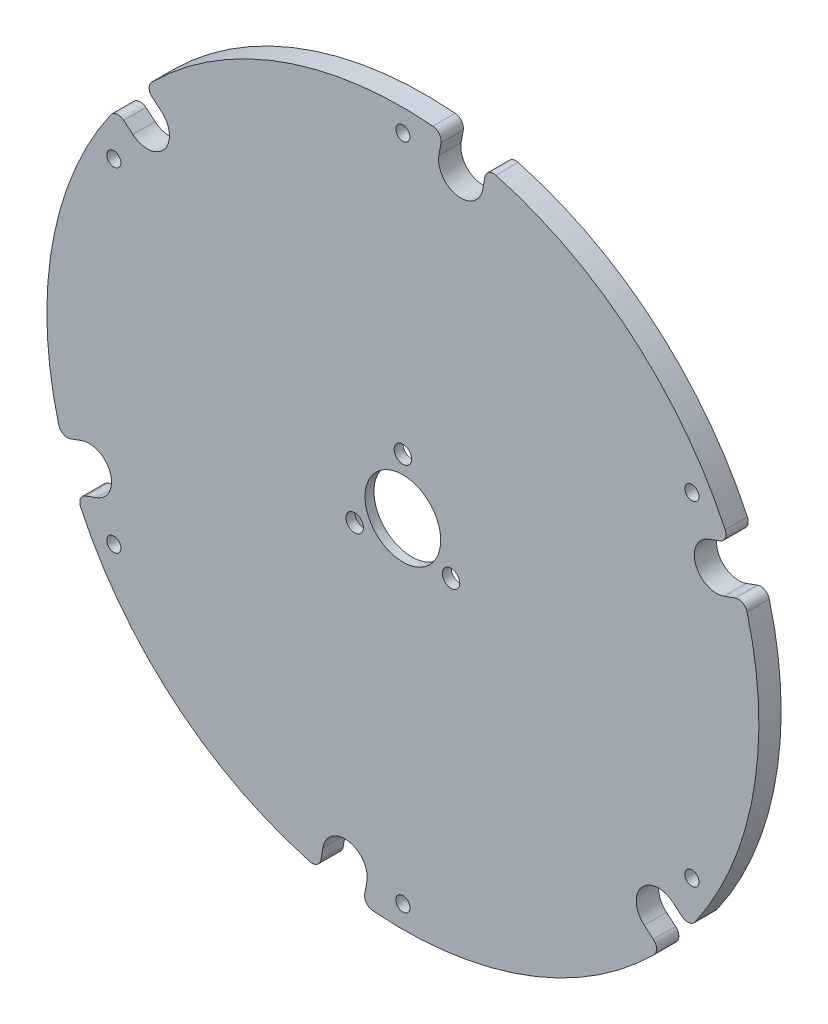
SolidWorks part; units mm, degrees
material "6061 Alloy"
ref_plane "Front Plane" through (0, 0, 0) normal (0, 0, 1) x (1, 0, 0)
ref_plane "Top Plane" through (0, 0, 0) normal (0, 1, 0) x (1, 0, 0)
ref_plane "Right Plane" through (0, 0, 0) normal (1, 0, 0) x (0, 0, -1)
sketch "Mount Plate Main" plane through (0, 0, 0) normal (0, 0, 1) x (1, 0, 0)
  line L0 (0, 0) -> (16.54, 93.8029) construction
  line L1 (0, 0) -> (0, 67.6211) construction
  line L2 (10.8786, 98.2641) -> (10.2865, 94.9056)
  line L3 (23.3857, 96.0587) -> (22.7935, 92.7003)
  line L4 (90.5385, 39.7109) -> (87.3339, 38.5445)
  line L5 (94.8822, 27.7768) -> (91.6776, 26.6104)
  line L6 (79.6599, -58.5532) -> (77.0474, -56.3611)
  line L7 (71.4965, -68.282) -> (68.884, -66.0899)
  line L8 (-10.8786, -98.2641) -> (-10.2865, -94.9056)
  line L9 (-23.3857, -96.0587) -> (-22.7935, -92.7003)
  line L10 (-90.5385, -39.7109) -> (-87.3339, -38.5445)
  line L11 (-94.8822, -27.7768) -> (-91.6776, -26.6104)
  line L12 (-79.6599, 58.5532) -> (-77.0474, 56.3611)
  line L13 (-71.4965, 68.282) -> (-68.884, 66.0899)
  arc A0 (8.592, 101.236) -> (-71.6552, 72.0285) centre (0, 0) ccw
  circle A1 centre (0, 0) radius 10.795
  circle A2 centre (0, 0) radius 19.685 construction
  arc A3 (10.8786, 98.2641) -> (8.592, 101.236) centre (8.3772, 98.7051) ccw
  arc A4 (10.2865, 94.9056) -> (22.7935, 92.7003) centre (16.54, 93.8029) ccw
  arc A5 (23.3857, 96.0587) -> (26.5509, 98.0694) centre (25.8871, 95.6177) cw
  arc A6 (90.5385, 39.7109) -> (91.969, 43.1771) centre (89.6698, 42.0977) ccw
  arc A7 (87.3339, 38.5445) -> (91.6776, 26.6104) centre (89.5057, 32.5774) ccw
  arc A8 (94.8822, 27.7768) -> (98.2061, 26.041) centre (95.7509, 25.3899) cw
  arc A9 (79.6599, -58.5532) -> (83.377, -58.0589) centre (81.2925, -56.6075) ccw
  arc A10 (77.0474, -56.3611) -> (68.884, -66.0899) centre (72.9657, -61.2255) ccw
  arc A11 (71.4965, -68.282) -> (71.6552, -72.0285) centre (69.8638, -70.2277) cw
  arc A12 (-10.8786, -98.2641) -> (-8.592, -101.236) centre (-8.3772, -98.7051) ccw
  arc A13 (-10.2865, -94.9056) -> (-22.7935, -92.7003) centre (-16.54, -93.8029) ccw
  arc A14 (-23.3857, -96.0587) -> (-26.5509, -98.0694) centre (-25.8871, -95.6177) cw
  arc A15 (-90.5385, -39.7109) -> (-91.969, -43.1771) centre (-89.6698, -42.0977) ccw
  arc A16 (-87.3339, -38.5445) -> (-91.6776, -26.6104) centre (-89.5057, -32.5774) ccw
  arc A17 (-94.8822, -27.7768) -> (-98.2061, -26.041) centre (-95.7509, -25.3899) cw
  arc A18 (-79.6599, 58.5532) -> (-83.377, 58.0589) centre (-81.2925, 56.6075) ccw
  arc A19 (-77.0474, 56.3611) -> (-68.884, 66.0899) centre (-72.9657, 61.2255) ccw
  arc A20 (-71.4965, 68.282) -> (-71.6552, 72.0285) centre (-69.8638, 70.2277) cw
  arc A21 (91.969, 43.1771) -> (26.5509, 98.0694) centre (0, 0) ccw
  arc A22 (83.377, -58.0589) -> (98.2061, 26.041) centre (0, 0) ccw
  arc A23 (-8.592, -101.236) -> (71.6552, -72.0285) centre (0, 0) ccw
  arc A24 (-91.969, -43.1771) -> (-26.5509, -98.0694) centre (0, 0) ccw
  arc A25 (-83.377, 58.0589) -> (-98.2061, -26.041) centre (0, 0) ccw
  point P3 (0, 95.25)
  point P4 (82.4889, 47.625)
  point P7 (82.4889, -47.625)
  point P8 (0, -95.25)
  point P9 (-82.4889, -47.625)
  point P10 (-82.4889, 47.625)
  point P11 (0, 0)
  point P12 (0, 15.875)
  point P16 (13.7482, -7.9375)
  point P17 (-13.7482, -7.9375)
  point P18 (0, 0)
  point P73 (0, 0)
  dimension "D1" = 203.2
  dimension "D4" = 39.37
  dimension "D5" = 21.59
  dimension "D10" = 2.54
  dimension "D2" = 95.25
  dimension "D6" = 15.875
  dimension "D8" = 10
  dimension "D9" = 95.25
  dimension "D11" = 6.35
  dimension "D3" = 6
  dimension "D7" = 3
  dimension "D12" = 6
extrude "Boss-Extrude1" add sketch "Mount Plate Main" against normal blind 6.35
hole_wizard "#9 (0.196) Diameter Hole1" positions "Sketch2" profile "Sketch3" hole size "#9" standard "ANSI Inch" end condition through all
sketch "Sketch2" plane through (0, 0, 0) normal (0, 0, 1) x (1, 0, 0)
  point P0 (0, 15.875)
  point P3 (13.7482, -7.9375)
  point P6 (-13.7482, -7.9375)
sketch "Sketch3" plane through (0, 15.875, 0) normal (1, 0, 0) x (0, -1, 0)
  line L0 (0, 0) -> (0, 6.35)
  line L1 (0, 6.35) -> (2.4892, 6.35)
  line L2 (2.4892, 6.35) -> (2.4892, 0)
  line L5 (2.4892, 0) -> (0, 0)
  line L11 (0, -6.35) -> (0, 107.95) construction
  dimension "Thru Hole Dia." = 4.9784
  dimension "Thru Hole Depth" = 6.35
hole_wizard "#10-32 Tapped Hole1" positions "Sketch4" profile "Sketch5" tap size "#10-32" standard "ANSI Inch" end condition through all
sketch "Sketch4" plane through (0, 0, 0) normal (0, 0, 1) x (1, 0, 0)
  point P0 (0, 95.25)
  point P3 (82.4889, 47.625)
  point P6 (82.4889, -47.625)
  point P9 (0, -95.25)
  point P12 (-82.4889, -47.625)
  point P15 (-82.4889, 47.625)
sketch "Sketch5" plane through (0, 95.25, 0) normal (1, 0, 0) x (0, -1, 0)
  line L0 (0, 0) -> (0, 6.35)
  line L1 (0, 6.35) -> (2.0193, 6.35)
  line L2 (2.0193, 6.35) -> (2.0193, 0)
  line L5 (2.0193, 0) -> (0, 0)
  line L11 (0, -6.35) -> (0, 107.95) construction
  dimension "Thru Tap Drill Dia." = 4.0386
  dimension "Thru Tap Drill Depth" = 6.35
cosmetic thread "Hole Thread1" parameters "D2"=4.826
cosmetic thread "Hole Thread2" parameters "D2"=4.826
cosmetic thread "Hole Thread3" parameters "D2"=4.826
cosmetic thread "Hole Thread4" parameters "D2"=4.826
cosmetic thread "Hole Thread5" parameters "D2"=4.826
cosmetic thread "Hole Thread6" parameters "D2"=4.826
sketch "Planet Mount CSink" plane through (0, 0, -6.35) normal (0, 0, -1) x (-1, 0, 0)
  circle A0 centre (0, 0) radius 19.685 construction
  circle A1 centre (0, 0) radius 19.685
extrude "Cut-Extrude1" cut sketch "Planet Mount CSink" against normal offset from surface (3.81 mm away) 2.54 up to face at (2.0193, 95.25, 0)
